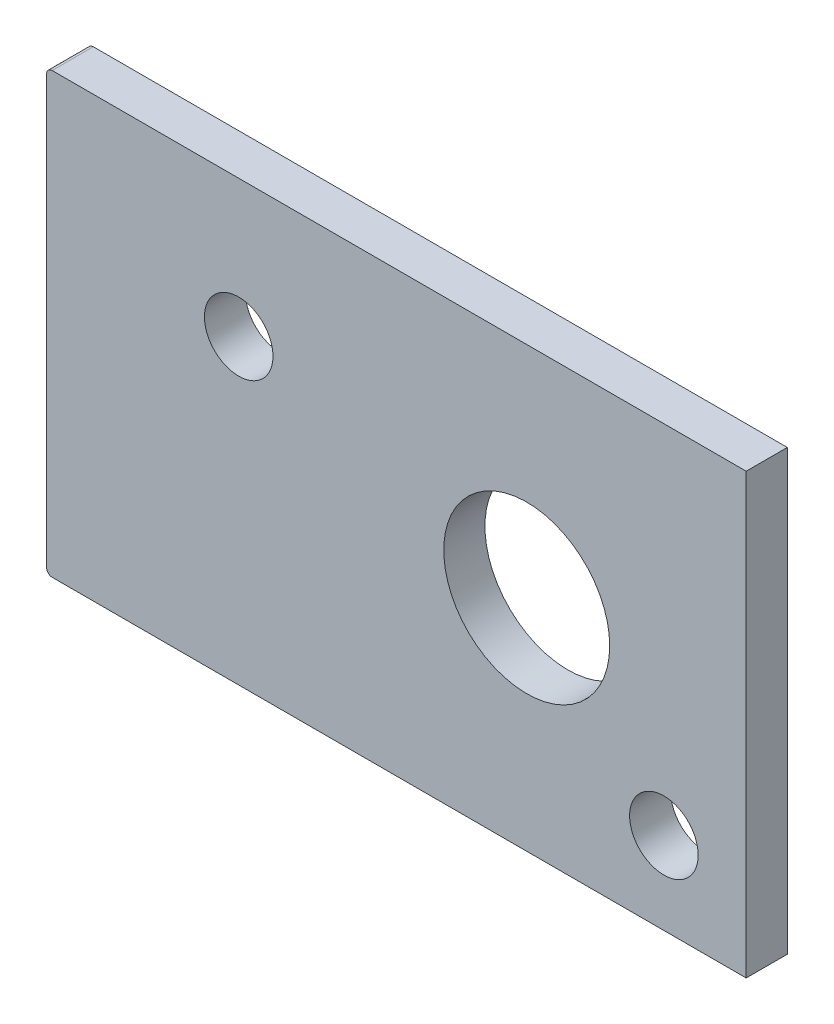
SolidWorks part; units mm, degrees
ref_plane "Front Plane" through (0, 0, 0) normal (0, 0, 1) x (1, 0, 0)
ref_plane "Top Plane" through (0, 0, 0) normal (0, 1, 0) x (1, 0, 0)
ref_plane "Right Plane" through (0, 0, 0) normal (1, 0, 0) x (0, 0, -1)
sketch "Sketch1" plane through (0, 0, 0) normal (0, 0, 1) x (1, 0, 0)
  line L0 (0, 16) -> (-25.3, 16)
  line L1 (0, 16) -> (0, 0)
  line L2 (0, 0) -> (-25.3, 0)
  line L3 (-25.5, 15.8) -> (-25.5, 0.2)
  arc A0 (-25.3, 16) -> (-25.5, 15.8) centre (-25.3, 15.8) ccw
  arc A1 (-25.3, 0) -> (-25.5, 0.2) centre (-25.3, 0.2) cw
  circle A2 centre (-3, 3) radius 1.25
  circle A5 centre (-8, 8) radius 3.025
  circle A6 centre (-18.5, 11) radius 1.25
  point P14 (0, 8)
  dimension "D1" = 0.2
  dimension "D2" = 3
  dimension "D6" = 7
  dimension "D7" = 11
  dimension "D8" = 2.5
  dimension "D10" = 8
  dimension "D11" = 6.05
  dimension "D3" = 13
  dimension "D4" = 25.5
  dimension "D5" = 16
base flange "Base-Flange1" sketch "Sketch1" thickness 1.5 reverse thickness direction no parameters "D1"=2
sketch "Bend-Lines1" [suppressed] plane through (0, 0, 0) normal (0, 1, 0) x (1, 0, 0)
sketch "Bounding-Box1" [suppressed] plane through (0, 0, 0) normal (0, 1, 0) x (1, 0, 0)
sheet metal parameters "Sheet-Metal1" thickness 1.5 parameters "D1"=2
flat pattern "Flat-Pattern1" [suppressed]
sketch "Bend-Lines2" plane through (0, 0, 0) normal (0, 1, 0) x (1, 0, 0)
sketch3d "Bounding-Box2" [suppressed]
  line L0 (-0.2, -0.2, 0) -> (25.3, -0.2, 0) construction
  line L1 (-0.2, 15.8, 0) -> (25.3, 15.8, 0) construction
  line L2 (-0.2, -0.2, 0) -> (-0.2, 15.8, 0) construction
  line L3 (25.3, -0.2, 0) -> (25.3, 15.8, 0) construction
